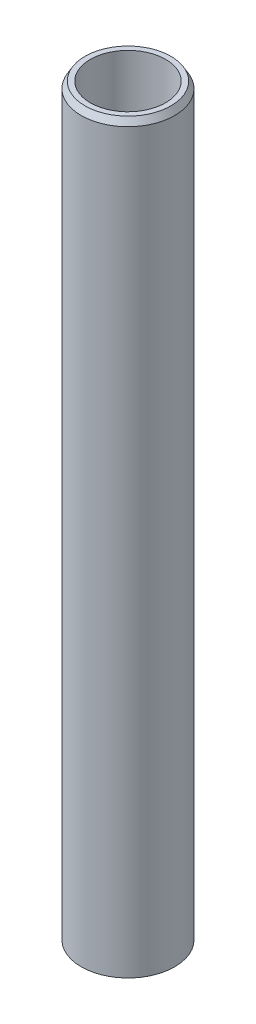
SolidWorks part; units mm, degrees
ref_plane "Front Plane" through (0, 0, 0) normal (0, 0, 1) x (1, 0, 0)
ref_plane "Top Plane" through (0, 0, 0) normal (0, 1, 0) x (1, 0, 0)
ref_plane "Right Plane" through (0, 0, 0) normal (1, 0, 0) x (0, 0, -1)
sketch "Sketch1" plane through (0, 0, 0) normal (0, 1, 0) x (1, 0, 0)
  circle A0 centre (0, 0) radius 37.5
  dimension "SHAFT_OD" = 75
extrude "Boss-Extrude1" add sketch "Sketch1" along normal blind 600
sketch "Sketch2" plane through (0, 0, 0) normal (0, 1, 0) x (1, 0, 0)
  circle A0 centre (0, 0) radius 30.2198
  dimension "BORE_D" = 60.4395
extrude "Cut-Extrude1" cut sketch "Sketch2" along normal through all
chamfer "Chamfer1" distance 5.2289 angle 30 2 edges at (0, 600, 37.5) (0, 0, 37.5) first distance on face at (0, 600, 37.5) first distance on face at (0, 0, 30.2198)
